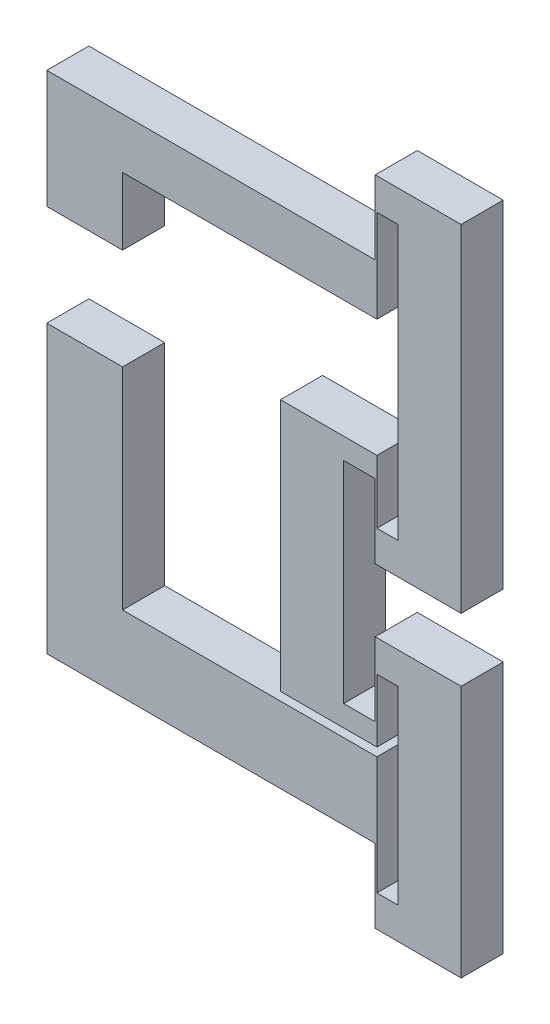
SolidWorks part; units mm, degrees
ref_plane "Front Plane" through (0, 0, 0) normal (0, 0, 1) x (1, 0, 0)
ref_plane "Top Plane" through (0, 0, 0) normal (0, 1, 0) x (1, 0, 0)
ref_plane "Right Plane" through (0, 0, 0) normal (1, 0, 0) x (0, 0, -1)
sketch "Sketch1" plane through (0, 0, 0) normal (0, 0, 1) x (1, 0, 0)
  line L0 (0, 0) -> (0, 34)
  line L4 (9, 9) -> (9, 34)
  line L5 (9, 34) -> (0, 34)
  line L6 (0, 46) -> (0, 60)
  line L7 (0, 60) -> (39, 60)
  line L8 (39.2, 60) -> (39.2, 54)
  line L9 (39.2, 54) -> (9, 54)
  line L10 (9, 54) -> (9, 46)
  line L11 (9, 46) -> (0, 46)
  line L12 (9, 9) -> (39.2, 9)
  line L20 (41.7, -5) -> (41.7, 17.5)
  line L24 (49.2, 21.25) -> (49.2, -8.75)
  line L32 (27.75, 10) -> (27.75, 40)
  line L33 (27.75, 40) -> (39.2, 40)
  line L36 (35.25, 37.5) -> (35.25, 12.5)
  line L41 (41.7, 65) -> (39.2, 65)
  line L44 (49.2, 68.75) -> (49.2, 28.75)
  line L47 (39.2, 60) -> (39.2, 65)
  line L48 (39, 60) -> (39, 68.75)
  line L49 (39, 68.75) -> (49.2, 68.75)
  line L55 (39.2, 40) -> (39.2, 37.5)
  line L78 (39.2, 32.5) -> (41.7, 32.5)
  line L82 (35.25, 37.5) -> (39, 37.5)
  line L83 (39.2, 37.5) -> (39.2, 32.5)
  line L84 (49.2, 28.75) -> (39, 28.75)
  line L85 (39, 28.75) -> (39, 37.5)
  line L86 (27.75, 10) -> (39.2, 10)
  line L87 (39.2, 10) -> (39.2, 12.5)
  line L88 (39, 12.5) -> (35.25, 12.5)
  line L89 (49.2, 21.25) -> (39, 21.25)
  line L90 (39, 21.25) -> (39, 19.8508)
  line L91 (39.2, 17.5) -> (41.7, 17.5)
  line L92 (39.2, 12.5) -> (39.2, 17.5)
  line L95 (39, 19.8508) -> (39, 12.5)
  line L97 (49.2, -8.75) -> (39, -8.75)
  line L98 (39, -8.75) -> (39, -5)
  line L100 (39, -5) -> (39, 0)
  line L101 (41.7, -5) -> (39.2, -5)
  line L105 (0, 0) -> (39, 0)
  line L106 (39.2, 9) -> (39.2, -3.1688)
  line L107 (39.2, -3.1688) -> (39.2, -5)
  line L108 (41.7, 65) -> (41.7, 32.5)
  dimension "D3" = 7.5
  dimension "D4" = 0.2
  dimension "D5" = 5
  dimension "D6" = 5
  dimension "D7" = 0.2
  dimension "D8" = 0.2
  dimension "D12" = 6
  dimension "D13" = 39
  dimension "D15" = 6
  dimension "D10" = 25
  dimension "D11" = 30
  dimension "D16" = 2.5
  dimension "D14" = 7.5
  dimension "D17" = 2.5
  dimension "D19" = 3.75
  dimension "D21" = 9
  dimension "D23" = 0.2
  dimension "D24" = 39
  dimension "D25" = 14
  dimension "D22" = 9
  dimension "D18" = 3.75
  dimension "D26" = 40
  dimension "D27" = 2.5
  dimension "D28" = 2.5
  dimension "D29" = 3.75
  dimension "D30" = 3.75
  dimension "D31" = 30
  dimension "D9" = 2.5
  dimension "D32" = 2.5
  dimension "D33" = 5
  dimension "D34" = 3.75
  dimension "D20" = 5
extrude "Boss-Extrude1" add sketch "Sketch1" along normal blind 5
equation "\"A.L\"= 0.03m"
equation "\"A.h\"= 0.0075m"
equation "\"A.d\"= 0.003m"
equation "\"A.delta\"= 45.0001"
equation "\"A.w\"= 0.05m"
equation "\"A.v\"= 0.05m"
equation "\"B.L\"= 0.04m"
equation "\"B.h\"= 0.0075m"
equation "\"C.h\"= 0.006m"
equation "\"C.d\"= 0.003m"
equation "\"C.L\"= 0.03m"
equation "\"C.wmax\"= 0.008m"
equation "\"a_h\"= 0.0002m"
equation "\"a_d\"= 0.003m"
equation "\"a_L\"= 0.005m"
equation "\"b_h\"= 0.0002m"
equation "\"b_d\"= 0.003m"
equation "\"b_L\"= 0.005m"
equation "\"c_h\"= 0.0002m"
equation "\"c_d\"= 0.003m"
equation "\"c_L\"= 0.005m"
equation "\"S.h\"= 0.009m"
equation "\"S.L\"= 0.08m"
equation "\"D4@Sketch1\"=\"c_h\""
equation "\"D5@Sketch1\"=\"c_L\""
equation "\"d_h\"= 0.0002m"
equation "\"d_L\"= 0.005m"
equation "\"d_d\"= 0.003m"
equation "\"D6@Sketch1\"=\"b_L\""
equation "\"D7@Sketch1\"=\"b_h\""
equation "\"D8@Sketch1\"=\"a_h\""
equation "\"D12@Sketch1\"=\"C.h\""
equation "\"D13@Sketch1\"=\"C.L\"+\"S.h\""
equation "\"D15@Sketch1\"=\"C.h\""
equation "\"A.t\"= \"A.h\" / 2"
equation "\"A.s\"= \"A.h\" / 3"
equation "\"D11@Sketch1\"=\"A.L\""
equation "\"D16@Sketch1\"=\"A.s\""
equation "\"D17@Sketch1\"=\"A.s\""
equation "\"D19@Sketch1\"=\"A.t\""
equation "\"D21@Sketch1\"=\"S.h\""
equation "\"D23@Sketch1\"=\"d_h\""
equation "\"D24@Sketch1\"=\"C.L\"+\"S.h\""
equation "\"D25@Sketch1\"=\"C.h\"+\"C.wmax\""
equation "\"D22@Sketch1\"=\"S.h\""
equation "\"D18@Sketch1\"=\"A.t\""
equation "\"B.t\"= \"B.h\" / 2"
equation "\"B.s\"= \"B.h\" / 3"
equation "\"D26@Sketch1\"=\"B.L\""
equation "\"D27@Sketch1\"=\"B.s\""
equation "\"D28@Sketch1\"=\"B.s\""
equation "\"D29@Sketch1\"=\"B.t\""
equation "\"D30@Sketch1\"=\"B.t\""
equation "\"D14@Sketch1\"=\"A.h\""
equation "\"D.L\"= 0.030m"
equation "\"D.h\"= 0.0075m"
equation "\"D.s\"= \"D.h\" / 2"
equation "\"D.t\"= \"D.h\" / 3"
equation "\"D31@Sketch1\"=\"D.L\""
equation "\"D3@Sketch1\"=\"D.h\""
equation "\"D9@Sketch1\"=\"D.t\""
equation "\"D33@Sketch1\"=\"a_L\""
equation "\"D34@Sketch1\"=\"D.s\""
equation "\"D32@Sketch1\"=\"D.t\""
equation "\"D20@Sketch1\"=\"d_L\""
